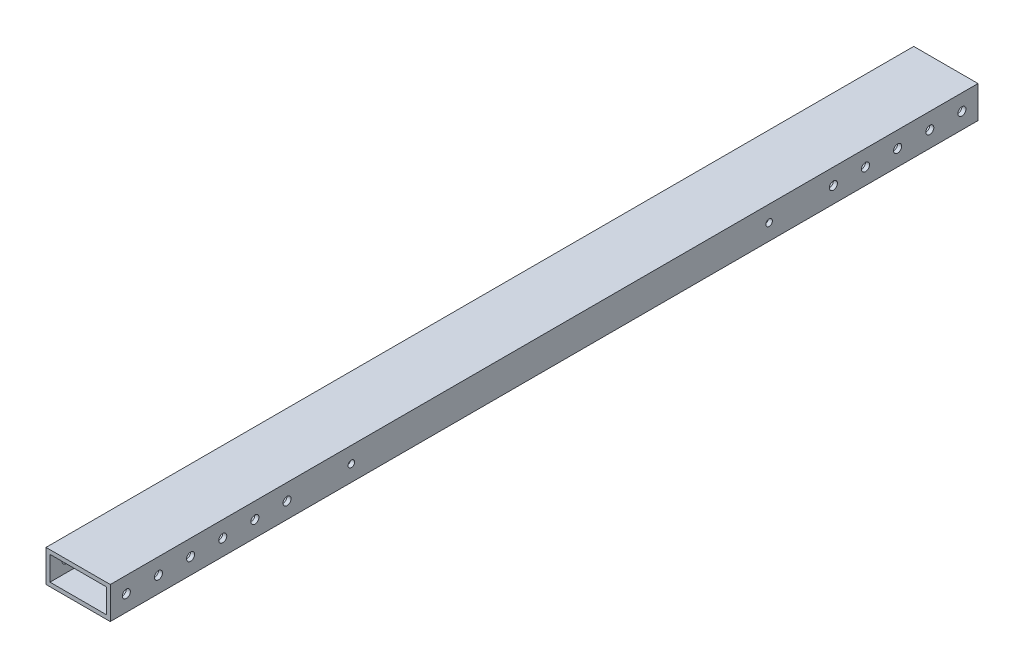
SolidWorks part; units mm, degrees
material "6061 Alloy"
ref_plane "Front Plane" through (0, 0, 0) normal (0, 0, 1) x (1, 0, 0)
ref_plane "Top Plane" through (0, 0, 0) normal (0, 1, 0) x (1, 0, 0)
ref_plane "Right Plane" through (0, 0, 0) normal (1, 0, 0) x (0, 0, -1)
sketch "Sketch1" plane through (0, 0, 0) normal (0, 0, 1) x (1, 0, 0)
  line L0 (-22.225, 9.525) -> (22.225, 9.525)
  line L2 (-25.4, 12.7) -> (25.4, 12.7)
  line L3 (-25.4, 12.7) -> (-25.4, -12.7)
  line L4 (-25.4, -12.7) -> (25.4, -12.7)
  line L5 (25.4, 12.7) -> (25.4, -12.7)
  line L10 (22.225, 9.525) -> (22.225, -9.525)
  line L11 (-22.225, -9.525) -> (22.225, -9.525)
  line L12 (-22.225, 9.525) -> (-22.225, -9.525)
  point P12 (0, 12.7)
  point P14 (25.4, 0)
  dimension "Wall Thickness" = 3.175
  dimension "Outside Width" = 50.8
  dimension "Outside Height" = 25.4
  dimension "Inside Height" = 19.05
  dimension "Inside Width" = 44.45
sketch "Sketch2" plane through (0, 0, 0) normal (1, 0, 0) x (0, 0, -1)
  line L0 (342.9, 0) -> (-342.9, 0)
  point P4 (0, 0)
  point P7 (-342.9, 0)
  point P10 (342.9, 0)
  dimension "Length" = 685.8
sketch "Sketch3" plane through (0, 0, 0) normal (0, 0, 1) x (1, 0, 0)
  line L21 (25.4, 12.7) -> (-25.4, 12.7)
  line L22 (25.4, -12.7) -> (25.4, 12.7)
  line L23 (-25.4, -12.7) -> (25.4, -12.7)
  line L24 (-25.4, 12.7) -> (-25.4, -12.7)
  line L25 (25.4, 12.7) -> (-25.4, 12.7)
  line L26 (25.4, -12.7) -> (25.4, 12.7)
  line L27 (-25.4, -12.7) -> (25.4, -12.7)
  line L28 (-25.4, 12.7) -> (-25.4, -12.7)
  line L29 (22.225, 9.525) -> (-22.225, 9.525)
  line L30 (22.225, -9.525) -> (22.225, 9.525)
  line L31 (-22.225, -9.525) -> (22.225, -9.525)
  line L32 (-22.225, 9.525) -> (-22.225, -9.525)
  line L33 (22.225, 9.525) -> (-22.225, 9.525)
  line L34 (22.225, -9.525) -> (22.225, 9.525)
  line L35 (-22.225, -9.525) -> (22.225, -9.525)
  line L36 (-22.225, 9.525) -> (-22.225, -9.525)
  dimension "D1" = 0
  dimension "D2" = 0
extrude "Boss-Extrude1" add sketch "Sketch3" along normal up to vertex (342.9 mm away) and the other way up to vertex (342.9 mm away) up to point (0, 0, 342.9) other way up to point (0, 0, -342.9)
sketch "Drawing Reference" plane through (0, 0, 0) normal (1, 0, 0) x (0, 0, -1)
  line L0 (-342.9, 0) -> (342.9, 0) construction
  line L1 (0, -12.7) -> (0, 12.7) construction
  line L2 (-342.9, -12.7) -> (342.9, -12.7) construction
  line L5 (-342.9, 12.7) -> (342.9, 12.7) construction
  point P7 (-306.324, 0)
  point P8 (306.324, 0)
  dimension "D1" = 36.576
sketch "Sketch5" plane through (25.4, 0, 0) normal (1, 0, 0) x (0, 0, -1)
  line L0 (-342.9, 0) -> (-279.4, 0)
  line L1 (-342.9, -12.7) -> (-342.9, 12.7) construction
  line L2 (-279.4, 0) -> (-254, 0)
  line L3 (-254, 0) -> (-228.6, 0)
  line L4 (-228.6, 0) -> (-203.2, 0)
sketch "Sketch8" plane through (25.4, 0, 0) normal (1, 0, 0) x (0, 0, -1)
  line L0 (342.9, 0) -> (304.8, 0)
  line L1 (342.9, -12.7) -> (342.9, 12.7) construction
  line L2 (304.8, 0) -> (279.4, 0)
  line L3 (279.4, 0) -> (254, 0)
  line L4 (254, 0) -> (228.6, 0)
  line L5 (342.9, 0) -> (330.2, 0)
hole_wizard "1/4 (0.25) Diameter Hole3" positions "Sketch12" profile "Sketch13" hole size "1/4" standard "ANSI Inch" end condition through all
sketch "Sketch12" plane through (-25.4, 0, 0) normal (-1, 0, 0) x (0, 0, 1)
  point P4 (-330.2, 0)
sketch "Sketch13" plane through (-25.4, 0, -330.2) normal (0, 1, 0) x (0, 0, 1)
  line L0 (0, 0) -> (0, 50.8)
  line L1 (0, 50.8) -> (3.175, 50.8)
  line L2 (3.175, 50.8) -> (3.175, 0)
  line L5 (3.175, 0) -> (0, 0)
  line L11 (0, -6.35) -> (0, 107.95) construction
  dimension "Thru Hole Dia." = 6.35
  dimension "Thru Hole Depth" = 50.8
hole_wizard "1/4 (0.25) Diameter Hole4" positions "Sketch14" profile "Sketch15" hole size "1/4" standard "ANSI Inch" end condition through all
sketch "Sketch14" plane through (-25.4, 0, 0) normal (-1, 0, 0) x (0, 0, 1)
  point P0 (304.8, 0)
  point P3 (330.2, 0)
sketch "Sketch15" plane through (-25.4, 0, 304.8) normal (0, 1, 0) x (0, 0, 1)
  line L0 (0, 0) -> (0, 50.8)
  line L1 (0, 50.8) -> (3.175, 50.8)
  line L2 (3.175, 50.8) -> (3.175, 0)
  line L5 (3.175, 0) -> (0, 0)
  line L11 (0, -6.35) -> (0, 107.95) construction
  dimension "Thru Hole Dia." = 6.35
  dimension "Thru Hole Depth" = 50.8
hole_wizard "1/4 (0.25) Diameter Hole5" positions "Sketch17" profile "Sketch18" hole size "1/4" standard "ANSI Inch" end condition through all
sketch "Sketch17" plane through (25.4, 0, 0) normal (1, 0, 0) x (0, 0, -1)
  point P0 (304.8, 0)
  point P3 (279.4, 0)
sketch "Sketch18" plane through (25.4, 0, -304.8) normal (0, 1, 0) x (0, 0, -1)
  line L0 (0, 0) -> (0, 50.8)
  line L1 (0, 50.8) -> (3.175, 50.8)
  line L2 (3.175, 50.8) -> (3.175, 0)
  line L5 (3.175, 0) -> (0, 0)
  line L11 (0, -6.35) -> (0, 107.95) construction
  dimension "Thru Hole Dia." = 6.35
  dimension "Thru Hole Depth" = 50.8
hole_wizard "1/4 (0.25) Diameter Hole6" positions "Sketch19" profile "Sketch20" hole size "1/4" standard "ANSI Inch" end condition through all
sketch "Sketch19" plane through (25.4, 0, 0) normal (1, 0, 0) x (0, 0, -1)
  point P0 (228.6, 0)
  point P3 (254, 0)
sketch "Sketch20" plane through (25.4, 0, -228.6) normal (0, 1, 0) x (0, 0, -1)
  line L0 (0, 0) -> (0, 50.8)
  line L1 (0, 50.8) -> (3.175, 50.8)
  line L2 (3.175, 50.8) -> (3.175, 0)
  line L5 (3.175, 0) -> (0, 0)
  line L11 (0, -6.35) -> (0, 107.95) construction
  dimension "Thru Hole Dia." = 6.35
  dimension "Thru Hole Depth" = 50.8
hole_wizard "1/4 (0.25) Diameter Hole7" positions "Sketch21" profile "Sketch22" hole size "1/4" standard "ANSI Inch" end condition through all
sketch "Sketch21" plane through (25.4, 0, 0) normal (1, 0, 0) x (0, 0, -1)
  point P0 (-203.2, 0)
  point P3 (-228.6, 0)
sketch "Sketch22" plane through (25.4, 0, 203.2) normal (0, 1, 0) x (0, 0, -1)
  line L0 (0, 0) -> (0, 50.8)
  line L1 (0, 50.8) -> (3.175, 50.8)
  line L2 (3.175, 50.8) -> (3.175, 0)
  line L5 (3.175, 0) -> (0, 0)
  line L11 (0, -6.35) -> (0, 107.95) construction
  dimension "Thru Hole Dia." = 6.35
  dimension "Thru Hole Depth" = 50.8
hole_wizard "1/4 (0.25) Diameter Hole8" positions "Sketch23" profile "Sketch24" hole size "1/4" standard "ANSI Inch" end condition through all
sketch "Sketch23" plane through (25.4, 0, 0) normal (1, 0, 0) x (0, 0, -1)
  point P0 (-279.4, 0)
  point P3 (-254, 0)
sketch "Sketch24" plane through (25.4, 0, 279.4) normal (0, 1, 0) x (0, 0, -1)
  line L0 (0, 0) -> (0, 50.8)
  line L1 (0, 50.8) -> (3.175, 50.8)
  line L2 (3.175, 50.8) -> (3.175, 0)
  line L5 (3.175, 0) -> (0, 0)
  line L11 (0, -6.35) -> (0, 107.95) construction
  dimension "Thru Hole Dia." = 6.35
  dimension "Thru Hole Depth" = 50.8
sketch "Sketch25" plane through (25.4, 0, 0) normal (1, 0, 0) x (0, 0, -1)
  line L0 (-203.2, 0) -> (-152.4, 0)
  line L1 (228.6, 0) -> (177.8, 0)
hole_wizard "13/64 (0.20313) Diameter Hole1" positions "Sketch26" profile "Sketch27" hole size "13/64" standard "ANSI Inch" end condition through all
sketch "Sketch26" plane through (25.4, 0, 0) normal (1, 0, 0) x (0, 0, -1)
  point P0 (-152.4, 0)
  point P3 (177.8, 0)
sketch "Sketch27" plane through (25.4, 0, 152.4) normal (0, 1, 0) x (0, 0, -1)
  line L0 (0, 0) -> (0, 50.8)
  line L1 (0, 50.8) -> (2.5798, 50.8)
  line L2 (2.5798, 50.8) -> (2.5798, 0)
  line L5 (2.5798, 0) -> (0, 0)
  line L11 (0, -6.35) -> (0, 107.95) construction
  dimension "Thru Hole Dia." = 5.1595
  dimension "Thru Hole Depth" = 50.8
sketch "Sketch30" plane through (-25.4, 0, 0) normal (-1, 0, 0) x (0, 0, 1)
  line L0 (203.2, 0) -> (184.15, 0)
  line L1 (203.2, 0) -> (152.4, 0) construction
  point P0 (-209.55, 0)
  point P2 (-209.55, 0)
hole_wizard "1/2 (0.5) Diameter Hole1" positions "Sketch33" profile "Sketch34" hole size "1/2" standard "ANSI Inch"
sketch "Sketch33" plane through (-25.4, 0, 0) normal (-1, 0, 0) x (0, 0, 1)
  point P0 (-209.55, 0)
  point P3 (184.15, 0)
sketch "Sketch34" plane through (-25.4, 0, -209.55) normal (0, 1, 0) x (0, 0, 1)
  line L0 (0, 0) -> (0, 10.1655)
  line L1 (0, 10.1655) -> (6.35, 6.35)
  line L2 (6.35, 6.35) -> (6.35, 0)
  line L5 (6.35, 0) -> (0, 0)
  line L10 (0, 10.1655) -> (-6.35, 6.35) construction
  line L11 (0, -6.35) -> (0, 107.95) construction
  dimension "Hole Dia." = 12.7
  dimension "Hole Depth" = 6.35
  dimension "Drill Angle" = 118
equation "\"D1@Drawing Reference\"=\"Outside Width@Sketch1\" * 0.72"
